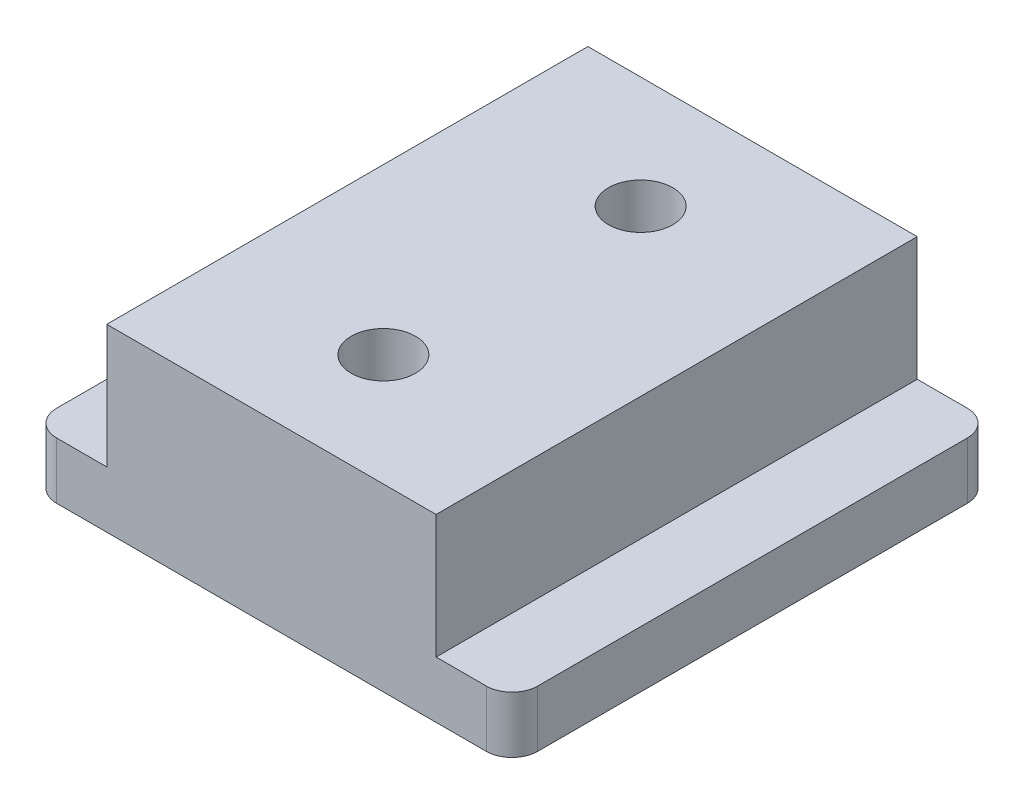
SolidWorks part; units mm, degrees
ref_plane "前视基准面" through (0, 0, 0) normal (0, 0, 1) x (1, 0, 0)
ref_plane "上视基准面" through (0, 0, 0) normal (0, 1, 0) x (1, 0, 0)
ref_plane "右视基准面" through (0, 0, 0) normal (1, 0, 0) x (0, 0, -1)
sketch "草图1" plane through (0, 0, 0) normal (0, 1, 0) x (1, 0, 0)
  line L0 (0, 5) -> (0, -5) construction
  line L1 (-8.35, 9.35) -> (8.35, 9.35)
  line L2 (-9.35, 8.35) -> (-9.35, -8.35)
  line L3 (-8.35, -9.35) -> (8.35, -9.35)
  line L4 (9.35, 8.35) -> (9.35, -8.35)
  line L5 (-9.35, 9.35) -> (9.35, -9.35) construction
  line L6 (-9.35, -9.35) -> (9.35, 9.35) construction
  line L7 (-6.4, 9.35) -> (6.4, 9.35)
  line L8 (-6.4, 9.35) -> (-6.4, -9.35)
  line L9 (-6.4, -9.35) -> (6.4, -9.35)
  line L10 (6.4, 9.35) -> (6.4, -9.35)
  line L11 (-6.4, 9.35) -> (6.4, -9.35) construction
  line L12 (-6.4, -9.35) -> (6.4, 9.35) construction
  arc A0 (8.35, 9.35) -> (9.35, 8.35) centre (8.35, 8.35) cw
  arc A1 (9.35, -8.35) -> (8.35, -9.35) centre (8.35, -8.35) cw
  arc A2 (-8.35, -9.35) -> (-9.35, -8.35) centre (-8.35, -8.35) cw
  arc A3 (-9.35, 8.35) -> (-8.35, 9.35) centre (-8.35, 8.35) cw
  circle A4 centre (0, 5) radius 2.5
  circle A5 centre (0, -5) radius 2.5
  circle A6 centre (0, 5) radius 1.25
  circle A7 centre (0, -5) radius 1.25
  point P0 (0, 0)
  point P6 (0, 0)
  dimension "D3" = 1
  dimension "D4" = 5
  dimension "D6" = 2.5
  dimension "D1" = 18.7
  dimension "D2" = 12.8
  dimension "D5" = 10
extrude "凸台-拉伸1" add sketch "草图1" along normal blind 2.2 contours A3 L2 A2 L3 L8 L1 | A1 L4 A0 L1 L10 L3 region at (-7.8652, 0, 0) region at (7.8652, 0, 0)
extrude "凸台-拉伸2" add sketch "草图1<3>" along normal blind 7 contours L10 L1 L8 L3 | A5 A7 | A4 A6 region at (0, 0, 0) region at (-2.4293, 0, -5) region at (-2.4293, 0, 5)
sketch "草图1<3>" plane through (0, 0, 0) normal (0, 1, 0) x (1, 0, 0) same geometry as "草图1"
extrude "切除-拉伸1" cut sketch "草图1<4>" along normal blind 2.2 contours A5 A7 | A4 A6 region at (-2.4293, 0, -5) region at (-2.4293, 0, 5)
sketch "草图1<4>" plane through (0, 0, 0) normal (0, 1, 0) x (1, 0, 0) same geometry as "草图1"
fillet "圆角1" radius 2 2 edges at (0, 2.2, -3.75) (0, 2.2, 6.25)
